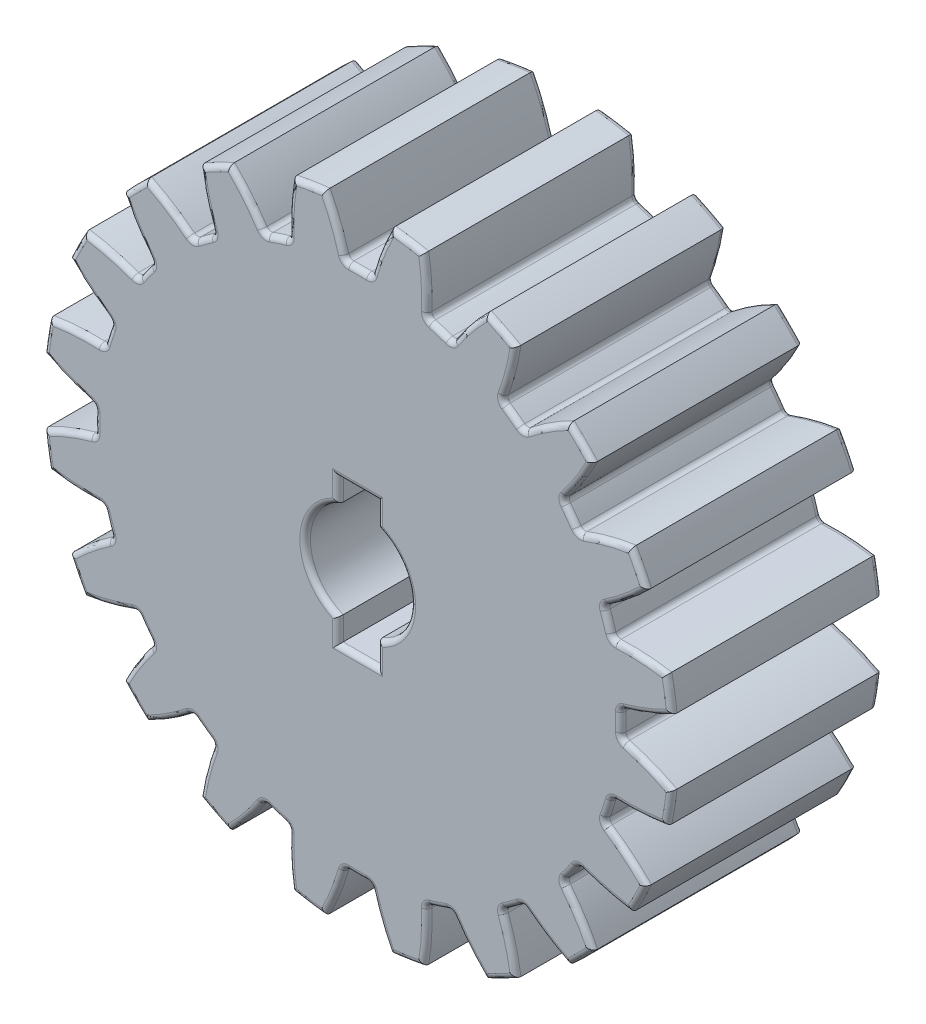
SolidWorks part; units mm, degrees
ref_plane "Front Plane" through (0, 0, 0) normal (0, 0, 1) x (1, 0, 0)
ref_plane "Top Plane" through (0, 0, 0) normal (0, 1, 0) x (1, 0, 0)
ref_plane "Right Plane" through (0, 0, 0) normal (1, 0, 0) x (0, 0, -1)
sketch "Sketch2" plane through (0, 0, 0) normal (0, 0, 1) x (1, 0, 0)
  line L1 (-0.75, -2.75) -> (0.75, -2.75)
  line L2 (-0.75, -2.75) -> (-0.75, 2.75)
  line L3 (-0.75, 2.75) -> (0.75, 2.75)
  line L4 (0.75, -2.75) -> (0.75, 2.75)
  line L5 (-0.75, -2.75) -> (0.75, 2.75) construction
  line L6 (-0.75, 2.75) -> (0.75, -2.75) construction
  circle A0 centre (0, 0) radius 11
  circle A1 centre (0, 0) radius 10
  circle A2 centre (0, 0) radius 2
  circle A3 centre (0, 0) radius 4
  circle A4 centre (0, 0) radius 5
  circle A5 centre (0, 0) radius 12
  dimension "D1" = 1.5
  dimension "D3" = 10
  dimension "D4" = 8
  dimension "D5" = 4
  dimension "D6" = 20
  dimension "D7" = 22
  dimension "D8" = 24
  dimension "D2" = 5.5
extrude "Boss-Extrude2" add sketch "Sketch2" along normal blind 8 contours A5 A0 | A0 A1 | A1 A4 | A3 A2 L2 L3 L4 L1 | A4 A3 region at (-10.6889, 0, 0) region at (-9.7172, 0, 0) region at (-3.8869, 0, 0) region at (-4.8586, 0, 0) region at (-11.6606, 0, 0)
extrude "Boss-Extrude4" add sketch "Sketch2<6>" along normal blind 2 and the other way blind 1 contours A4 | A3
sketch "Sketch2<6>" plane through (0, 0, 0) normal (0, 0, 1) x (1, 0, 0) same geometry as "Sketch2"
extrude "Boss-Extrude5" add sketch "Sketch2<7>" along normal blind 3 contours A4 | A3
sketch "Sketch2<7>" plane through (0, 0, 0) normal (0, 0, 1) x (1, 0, 0) same geometry as "Sketch2"
sketch "Sketch3" plane through (0, 0, 0) normal (0, 0, -1) x (-1, 0, 0)
  line L0 (0, 0) -> (0, 16.7104) construction
  arc A0 (-0.3411, 9.9942) -> (0.3411, 9.9942) centre (0, 0) cw
  circle A1 centre (0, 0) radius 10 construction
  arc A2 (0.5407, 10.1408) -> (5.604, 15.9875) centre (9.2157, 7.744) cw
  arc A3 (-0.5407, 10.1408) -> (-5.604, 15.9875) centre (-9.2157, 7.744) ccw
  arc A4 (-5.604, 15.9875) -> (5.604, 15.9875) centre (0, -7.9439) cw
  arc A5 (-0.5407, 10.1408) -> (-0.3411, 9.9942) centre (-0.348, 10.1941) ccw
  arc A6 (0.3411, 9.9942) -> (0.5407, 10.1408) centre (0.348, 10.1941) ccw
  point P15 (-0.4998, 9.9875)
  point P18 (0.4998, 9.9875)
  dimension "D1" = 0.2
  dimension "D3" = 9
  dimension "D2" = 6
extrude "Cut-Extrude1" cut sketch "Sketch3" against normal through all both and the other way through all
pattern_circular "CirPattern1" count 20 over 360 about axis through (0, 0, 8) along (0, 0, -1) of "Cut-Extrude1" reverse direction yes
fillet "Fillet3" radius 0.2 260 edges at (-8.4853, 8.4853, 8) (-7.1848, 8.4469, 8) (-6.2745, 7.8426, 8) (-5.8779, 8.0902, 8) (-5.5199, 8.3909, 8) (-5.8133, 9.4434, 8) (-5.4479, 10.6921, 8) (-4.2229, 10.2537, 8) (-3.5439, 9.3977, 8) (-3.0902, 9.5106, 8) (-2.6568, 9.686, 8) (-2.6106, 10.7776, 8) (-1.8772, 11.8523, 8) (-0.8476, 11.0568, 8) (-0.4664, 10.0329, 8) (0, 10, 8) (0.4664, 10.0329, 8) (0.8476, 11.0568, 8) (1.8772, 11.8523, 8) (2.6106, 10.7776, 8) (2.6568, 9.686, 8) (3.0902, 9.5106, 8) (3.5439, 9.3977, 8) (4.2229, 10.2537, 8) (5.4479, 10.6921, 8) (5.8133, 9.4434, 8) (5.5199, 8.3909, 8) (5.8779, 8.0902, 8) (6.2745, 7.8426, 8) (7.1848, 8.4469, 8) (8.4853, 8.4853, 8) (8.4469, 7.1848, 8) (7.8426, 6.2745, 8) (8.0902, 5.8779, 8) (8.3909, 5.5199, 8) (9.4434, 5.8133, 8) (10.6921, 5.4479, 8) (10.2537, 4.2229, 8) (9.3977, 3.5439, 8) (9.5106, 3.0902, 8) (9.686, 2.6568, 8) (10.7776, 2.6106, 8) (11.8523, 1.8772, 8) (11.0568, 0.8476, 8) (10.0329, 0.4664, 8) (10, 0, 8) (10.0329, -0.4664, 8) (11.0568, -0.8476, 8) (11.8523, -1.8772, 8) (10.7776, -2.6106, 8) (9.686, -2.6568, 8) (9.5106, -3.0902, 8) (9.3977, -3.5439, 8) (10.2537, -4.2229, 8) (10.6921, -5.4479, 8) (9.4434, -5.8133, 8) (8.3909, -5.5199, 8) (8.0902, -5.8779, 8) (7.8426, -6.2745, 8) (8.4469, -7.1848, 8) (8.4853, -8.4853, 8) (7.1848, -8.4469, 8) (6.2745, -7.8426, 8) (5.8779, -8.0902, 8) (5.5199, -8.3909, 8) (5.8133, -9.4434, 8) (5.4479, -10.6921, 8) (4.2229, -10.2537, 8) (3.5439, -9.3977, 8) (3.0902, -9.5106, 8) (2.6568, -9.686, 8) (2.6106, -10.7776, 8) (1.8772, -11.8523, 8) (0.8476, -11.0568, 8) (0.4664, -10.0329, 8) (0, -10, 8) (-0.4664, -10.0329, 8) (-0.8476, -11.0568, 8) (-1.8772, -11.8523, 8) (-2.6106, -10.7776, 8) (-2.6568, -9.686, 8) (-3.0902, -9.5106, 8) (-3.5439, -9.3977, 8) (-4.2229, -10.2537, 8) (-5.4479, -10.6921, 8) (-5.8133, -9.4434, 8) (-5.5199, -8.3909, 8) (-5.8779, -8.0902, 8) (-6.2745, -7.8426, 8) (-7.1848, -8.4469, 8) (-8.4853, -8.4853, 8) (-8.4469, -7.1848, 8) (-7.8426, -6.2745, 8) (-8.0902, -5.8779, 8) (-8.3909, -5.5199, 8) (-9.4434, -5.8133, 8) (-10.6921, -5.4479, 8) (-10.2537, -4.2229, 8) (-9.3977, -3.5439, 8) (-9.5106, -3.0902, 8) (-9.686, -2.6568, 8) (-10.7776, -2.6106, 8) (-11.8523, -1.8772, 8) (-11.0568, -0.8476, 8) (-10.0329, -0.4664, 8) (-10, 0, 8) (-10.0329, 0.4664, 8) (-11.0568, 0.8476, 8) (-11.8523, 1.8772, 8) (-10.7776, 2.6106, 8) (-9.686, 2.6568, 8) (-9.5106, 3.0902, 8) (-9.3977, 3.5439, 8) (-10.2537, 4.2229, 8) (-10.6921, 5.4479, 8) (-9.4434, 5.8133, 8) (-8.3909, 5.5199, 8) (-8.0902, 5.8779, 8) (-7.8426, 6.2745, 8) (-8.4469, 7.1848, 8) (-0.75, -2.302, 8) (0, -2.75, 8) (0.75, -2.302, 8) (2, 0, 8) (0.75, 2.302, 8) (0, 2.75, 8) (-0.75, 2.302, 8) (-2, 0, 8) (4, 0, 0) (-0.75, 2.302, 0) (0, 2.75, 0) (0.75, 2.302, 0) (2, 0, 0) (0.75, -2.302, 0) (0, -2.75, 0) (-0.75, -2.302, 0) (-2, 0, 0) (5, 0, -1) (4, 0, -1) (-8.0902, 5.8779, 0) (-8.3909, 5.5199, 0) (-9.4434, 5.8133, 0) (-10.6921, 5.4479, 0) (-10.2537, 4.2229, 0) (-9.3977, 3.5439, 0) (-9.5106, 3.0902, 0) (-9.686, 2.6568, 0) (-10.7776, 2.6106, 0) (-11.8523, 1.8772, 0) (-11.0568, 0.8476, 0) (-10.0329, 0.4664, 0) (-10, 0, 0) (-10.0329, -0.4664, 0) (-11.0568, -0.8476, 0) (-11.8523, -1.8772, 0) (-10.7776, -2.6106, 0) (-9.686, -2.6568, 0) (-9.5106, -3.0902, 0) (-9.3977, -3.5439, 0) (-10.2537, -4.2229, 0) (-10.6921, -5.4479, 0) (-9.4434, -5.8133, 0) (-8.3909, -5.5199, 0) (-8.0902, -5.8779, 0) (-7.8426, -6.2745, 0) (-8.4469, -7.1848, 0) (-8.4853, -8.4853, 0) (-7.1848, -8.4469, 0) (-6.2745, -7.8426, 0) (-5.8779, -8.0902, 0) (-5.5199, -8.3909, 0) (-5.8133, -9.4434, 0) (-5.4479, -10.6921, 0) (-4.2229, -10.2537, 0) (-3.5439, -9.3977, 0) (-3.0902, -9.5106, 0) (-2.6568, -9.686, 0) (-2.6106, -10.7776, 0) (-1.8772, -11.8523, 0) (-0.8476, -11.0568, 0) (-0.4664, -10.0329, 0) (0, -10, 0) (0.4664, -10.0329, 0) (0.8476, -11.0568, 0) (1.8772, -11.8523, 0) (2.6106, -10.7776, 0) (2.6568, -9.686, 0) (3.0902, -9.5106, 0) (3.5439, -9.3977, 0) (4.2229, -10.2537, 0) (5.4479, -10.6921, 0) (5.8133, -9.4434, 0) (5.5199, -8.3909, 0) (5.8779, -8.0902, 0) (6.2745, -7.8426, 0) (7.1848, -8.4469, 0) (8.4853, -8.4853, 0) (8.4469, -7.1848, 0) (7.8426, -6.2745, 0) (8.0902, -5.8779, 0) (8.3909, -5.5199, 0) (9.4434, -5.8133, 0) (10.6921, -5.4479, 0) (10.2537, -4.2229, 0) (9.3977, -3.5439, 0) (9.5106, -3.0902, 0) (9.686, -2.6568, 0) (10.7776, -2.6106, 0) (11.8523, -1.8772, 0) (11.0568, -0.8476, 0) (10.0329, -0.4664, 0) (10, 0, 0) (10.0329, 0.4664, 0) (11.0568, 0.8476, 0) (11.8523, 1.8772, 0) (10.7776, 2.6106, 0) (9.686, 2.6568, 0) (9.5106, 3.0902, 0) (9.3977, 3.5439, 0) (10.2537, 4.2229, 0) (10.6921, 5.4479, 0) (9.4434, 5.8133, 0) (8.3909, 5.5199, 0) (8.0902, 5.8779, 0) (7.8426, 6.2745, 0) (8.4469, 7.1848, 0) (8.4853, 8.4853, 0) (7.1848, 8.4469, 0) (6.2745, 7.8426, 0) (5.8779, 8.0902, 0) (5.5199, 8.3909, 0) (5.8133, 9.4434, 0) (5.4479, 10.6921, 0) (4.2229, 10.2537, 0) (3.5439, 9.3977, 0) (3.0902, 9.5106, 0) (2.6568, 9.686, 0) (2.6106, 10.7776, 0) (1.8772, 11.8523, 0) (0.8476, 11.0568, 0) (0.4664, 10.0329, 0) (0, 10, 0) (-0.4664, 10.0329, 0) (-0.8476, 11.0568, 0) (-1.8772, 11.8523, 0) (-2.6106, 10.7776, 0) (-2.6568, 9.686, 0) (-3.0902, 9.5106, 0) (-3.5439, 9.3977, 0) (-4.2229, 10.2537, 0) (-5.4479, 10.6921, 0) (-5.8133, 9.4434, 0) (-5.5199, 8.3909, 0) (-5.8779, 8.0902, 0) (-6.2745, 7.8426, 0) (-7.1848, 8.4469, 0) (-8.4853, 8.4853, 0) (-8.4469, 7.1848, 0) (-7.8426, 6.2745, 0) (5, 0, 0)
